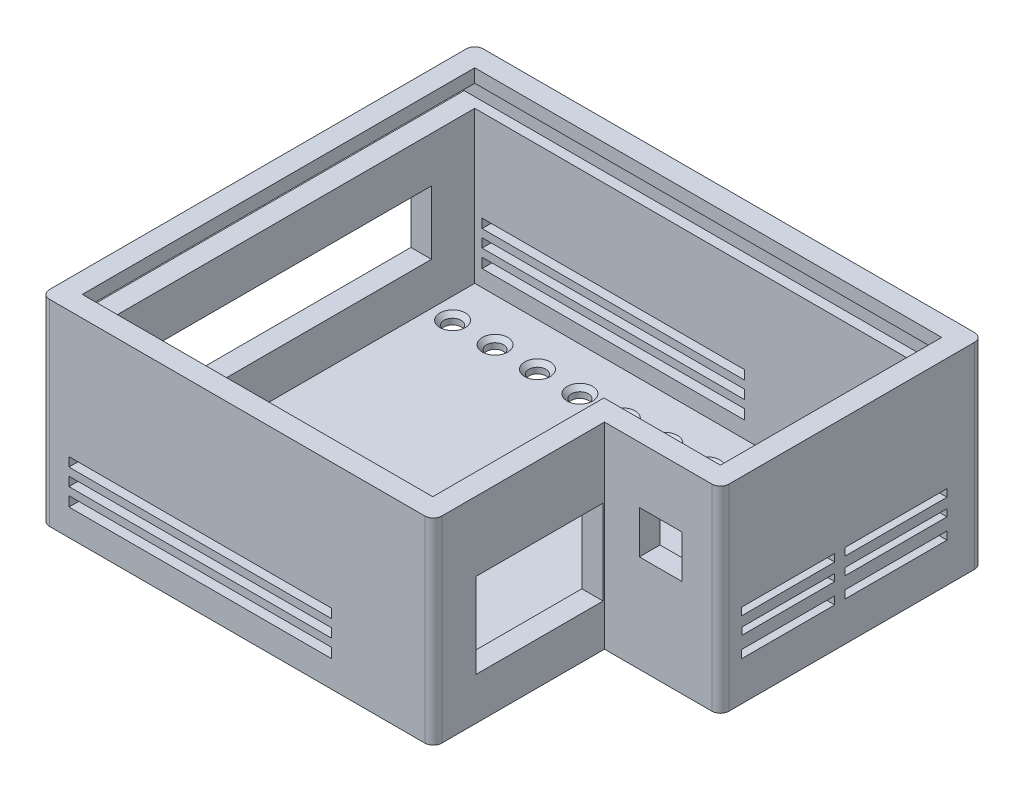
SolidWorks part; units mm, degrees
ref_plane "Front Plane" through (0, 0, 0) normal (0, 0, 1) x (1, 0, 0)
ref_plane "Top Plane" through (0, 0, 0) normal (0, 1, 0) x (1, 0, 0)
ref_plane "Right Plane" through (0, 0, 0) normal (1, 0, 0) x (0, 0, -1)
sketch "Sketch1" plane through (0, 0, 0) normal (0, 1, 0) x (1, 0, 0)
  line L0 (104.775, 0) -> (139.775, 0)
  line L1 (0, 0) -> (104.775, 0)
  line L2 (0, 0) -> (0, -117.475)
  line L3 (0, -117.475) -> (104.902, -117.475)
  line L4 (104.902, -66.2424) -> (104.902, -117.475)
  line L5 (139.775, 0) -> (139.775, -66.2424)
  line L6 (-3, -120.475) -> (104.902, -120.475)
  line L7 (104.902, -117.475) -> (104.902, -66.2424)
  line L8 (104.902, -66.2424) -> (139.775, -66.2424)
  line L9 (-3, 3) -> (-3, -120.475)
  line L10 (-3, 3) -> (104.775, 3)
  line L11 (104.775, 3) -> (142.775, 3)
  line L12 (142.775, 3) -> (142.775, -69.2424)
  line L13 (108.077, -69.2424) -> (142.775, -69.2424)
  line L14 (104.902, -66.2424) -> (107.9494, -66.2424)
  line L16 (108.077, -120.475) -> (104.902, -120.475)
  line L17 (-6.175, 6.175) -> (-6.175, -123.65)
  line L18 (104.902, -69.2424) -> (142.775, -69.2424) construction
  line L19 (-6.175, -123.65) -> (104.902, -123.65)
  line L20 (111.252, -123.65) -> (104.902, -123.65)
  line L21 (111.252, -72.4174) -> (111.252, -123.65)
  line L22 (111.252, -72.4174) -> (145.95, -72.4174)
  line L23 (145.95, 6.175) -> (145.95, -72.4174)
  line L24 (104.775, 6.175) -> (145.95, 6.175)
  line L25 (-6.175, 6.175) -> (104.775, 6.175)
  line L26 (108.077, -69.2424) -> (108.077, -120.475) construction
  dimension "D1" = 104.775
  dimension "D2" = 117.475
  dimension "D3" = 35
  dimension "D5" = 104.902
  dimension "D6" = 51.2326
  dimension "D8" = 51.2326
  dimension "D4" = 3
  dimension "D7" = 3.175
extrude "Boss-Extrude1" add sketch "Sketch1" along normal blind 55.88 contours L8 L4 L13 L12 L11 L10 L9 L6 L16 L7 L3 L2 L1 L0 L5 region at (49.3, 0, -4.1751)
ref_plane "Plane1" through (0, 0, 0) normal (0, 0, 1) x (1, 0, 0)
sketch "Sketch23" plane through (0, 0, 72.4174) normal (0, 0, 1) x (1, 0, 0)
  line L9 (121.6901, 38.9689) -> (134.3901, 38.9689)
  line L10 (121.6901, 38.9689) -> (121.6901, 26.1561)
  line L11 (121.6901, 26.1561) -> (134.3901, 26.1561)
  line L12 (134.3901, 38.9689) -> (134.3901, 26.1561)
  dimension "D1" = 12.8128
  dimension "D2" = 12.7
sketch "Sketch25" plane through (-6.175, 0, 0) normal (-1, 0, 0) x (0, 0, 1)
  line L1 (-6.175, 55.88) -> (-6.175, 0) construction
  line L4 (12.9455, 12.7) -> (101.8455, 12.7)
  line L5 (12.9455, 12.7) -> (12.9455, 31.75)
  line L6 (12.9455, 31.75) -> (101.8455, 31.75)
  line L7 (101.8455, 12.7) -> (101.8455, 31.75)
  dimension "D1" = 88.9
  dimension "D2" = 19.05
  dimension "D3" = 19.1205
extrude "Cut-Extrude9" cut sketch "Sketch25" against normal blind 45
sketch "Sketch26" plane through (145.95, 0, 0) normal (1, 0, 0) x (0, 0, -1)
  line L0 (-35.1213, 22.0738) -> (-4.5981, 22.0738)
  line L1 (-66.1038, 11.0882) -> (-38.1973, 11.0882)
  line L2 (-66.1038, 11.0882) -> (-66.1038, 8.7152)
  line L3 (-66.1038, 8.7152) -> (-38.1973, 8.7152)
  line L4 (-4.5981, 11.0882) -> (-4.5981, 8.7152)
  line L5 (-65.9512, 14.7529) -> (-38.1973, 14.7529)
  line L6 (-65.9512, 14.7529) -> (-65.9512, 16.8722)
  line L7 (-65.9512, 16.8722) -> (-38.1973, 16.8722)
  line L8 (-4.5981, 14.7529) -> (-4.5981, 16.8722)
  line L9 (-66.0841, 19.8363) -> (-38.1973, 19.8363)
  line L10 (-66.0841, 19.8363) -> (-66.0841, 22.0738)
  line L11 (-66.0841, 22.0738) -> (-38.1973, 22.0738)
  line L12 (-4.5981, 19.8363) -> (-4.5981, 22.0738)
  line L14 (-38.1973, 22.0738) -> (-38.1973, 19.8363)
  line L16 (-35.1213, 22.0738) -> (-35.1213, 19.8363)
  line L17 (-35.1213, 19.8363) -> (-4.5981, 19.8363)
  line L18 (-35.1213, 16.8722) -> (-35.1213, 14.7529)
  line L19 (-38.1973, 16.8722) -> (-38.1973, 14.7529)
  line L20 (-35.1213, 8.7152) -> (-4.5981, 8.7152)
  line L21 (-35.1213, 11.0882) -> (-4.5981, 11.0882)
  line L22 (-35.1213, 11.0882) -> (-35.1213, 8.7152)
  line L23 (-38.1973, 11.0882) -> (-38.1973, 8.7152)
  line L24 (-35.1213, 14.7529) -> (-4.5981, 14.7529)
  line L25 (-35.1213, 16.8722) -> (-4.5981, 16.8722)
extrude "Cut-Extrude10" cut sketch "Sketch26" against normal blind 45
sketch "Sketch27" plane through (0, 0, -6.175) normal (0, 0, -1) x (-1, 0, 0)
  line L1 (-2.1913, 4.9397) -> (-80.721, 4.9397)
  line L2 (-2.1913, 4.9397) -> (-2.1913, 7.8744)
  line L3 (-2.1913, 7.8744) -> (-80.721, 7.8744)
  line L4 (-80.721, 4.9397) -> (-80.721, 7.8744)
  line L5 (-80.721, 10.2406) -> (-2.1913, 10.2406)
  line L6 (-80.721, 10.2406) -> (-80.721, 12.9398)
  line L7 (-80.721, 12.9398) -> (-2.1913, 12.9398)
  line L8 (-2.1913, 10.2406) -> (-2.1913, 12.9398)
  line L9 (-2.1913, 15.306) -> (-80.721, 15.306)
  line L10 (-2.1913, 15.306) -> (-2.1913, 18.0154)
  line L11 (-2.1913, 18.0154) -> (-80.721, 18.0154)
  line L12 (-80.721, 15.306) -> (-80.721, 18.0154)
extrude "Cut-Extrude11" cut sketch "Sketch27" against normal blind 254
extrude "Cut-Extrude12" cut sketch "Sketch23" against normal blind 50.8
sketch "Sketch31" plane through (-6.175, 0, 0) normal (-1, 0, 0) x (0, 0, 1)
  line L3 (-3, 45.3704) -> (-3, 51.8754)
  line L4 (-3, 51.8754) -> (120.5647, 51.8754)
  line L7 (120.5647, 51.8754) -> (120.5647, 45.3704)
  line L8 (120.5647, 45.3704) -> (-3, 45.3704)
extrude "Cut-Extrude13" cut sketch "Sketch31" against normal blind 113.8
sketch "Sketch34" plane through (107.625, 0, 0) normal (-1, 0, 0) x (0, 0, 1)
  line L1 (66.2424, 45.3704) -> (69.0364, 45.3704)
  line L2 (66.2424, 45.3704) -> (66.2424, 51.3704)
  line L3 (66.2424, 51.3704) -> (69.0364, 51.3704)
  line L4 (69.0364, 45.3704) -> (69.0364, 51.3704)
  line L5 (-3, 45.3704) -> (0, 45.3704)
  line L6 (-3, 45.3704) -> (-3, 51.8754)
  line L7 (-3, 51.8754) -> (0, 51.8754)
  line L8 (0, 45.3704) -> (0, 51.8754)
  dimension "D1" = 6
  dimension "D2" = 2.794
extrude "Cut-Extrude14" cut sketch "Sketch34" against normal blind 35.8
sketch "Sketch35" plane through (139.775, 0, 0) normal (-1, 0, 0) x (0, 0, 1)
  line L1 (0, 45.3704) -> (66.2424, 45.3704)
  line L2 (0, 45.3704) -> (0, 51.3704)
  line L3 (0, 51.3704) -> (66.2424, 51.3704)
  line L4 (66.2424, 45.3704) -> (66.2424, 51.3704)
extrude "Cut-Extrude15" cut sketch "Sketch35" against normal blind 2.8
sketch "Sketch36" plane through (0, 0, 0) normal (0, -1, 0) x (1, 0, 0)
  line L0 (111.252, 72.4174) -> (111.252, 123.65)
  line L1 (111.252, 123.65) -> (-6.175, 123.65)
  line L2 (-6.175, 123.65) -> (-6.175, -6.175)
  line L3 (-6.175, -6.175) -> (145.95, -6.175)
  line L4 (145.95, -6.175) -> (145.95, 72.4174)
  line L5 (145.95, 72.4174) -> (111.252, 72.4174)
extrude "Boss-Extrude2" add sketch "Sketch36" along normal blind 3
ref_plane "Plane2" through (145.95, -3, 72.4174) normal (0, -1, 0) x (-1, 0, 0)
sketch "Sketch37" plane through (145.95, -3, 72.4174) normal (0, -1, 0) x (1, 0, 0)
  line L0 (0, -78.5924) -> (0, 0) construction
  line L1 (-152.125, -78.5924) -> (0, -78.5924) construction
  circle A22 centre (-12.7, -59.5424) radius 2.54
  circle A26 centre (-63.5, 29.3576) radius 2.54
  circle A27 centre (-114.3, 29.3576) radius 2.54
  circle A28 centre (-25.4, -59.5424) radius 2.54
  circle A29 centre (-38.1, -59.5424) radius 2.54
  circle A30 centre (-50.8, -59.5424) radius 2.54
  circle A31 centre (-63.5, -59.5424) radius 2.54
  circle A32 centre (-76.2, -59.5424) radius 2.54
  circle A33 centre (-88.9, -59.5424) radius 2.54
  circle A34 centre (-101.6, -59.5424) radius 2.54
  circle A35 centre (-114.3, -59.5424) radius 2.54
  circle A36 centre (-127, -59.5424) radius 2.54
  circle A37 centre (-139.7, -59.5424) radius 2.54
  dimension "D1" = 5.08
  dimension "D2" = 12.7
  dimension "D3" = 19.05
  dimension "D5" = 88.9
  dimension "D7" = 5.08
  dimension "D8" = 5.08
  dimension "D9" = 11
  dimension "D12" = 88.9
  dimension "D15" = 50.8
sketch "Sketch38" plane through (111.252, 0, 0) normal (1, 0, 0) x (0, 0, -1)
  line L0 (-72.4174, -3) -> (-123.65, -3) construction
  line L1 (-110.95, 35.1) -> (-72.85, 35.1)
  line L2 (-110.95, 35.1) -> (-110.95, 9.7)
  line L3 (-110.95, 9.7) -> (-72.85, 9.7)
  line L4 (-72.85, 35.1) -> (-72.85, 9.7)
  line L5 (-123.65, 55.88) -> (-123.65, -3) construction
  dimension "D1" = 12.7
  dimension "D2" = 12.7
  dimension "D3" = 50.8
  dimension "D4" = 38.1
extrude "Cut-Extrude17" cut sketch "Sketch38" against normal blind 10.16
fillet "Fillet1" radius 2.54 5 edges at (-6.175, 26.44, 123.65) (-6.175, 26.44, -6.175) (111.252, 26.44, 123.65) (145.95, 26.44, 72.4174) (145.95, 26.44, -6.175)
extrude "Cut-Extrude18" cut sketch "Sketch37" against normal blind 5.842
chamfer "Chamfer1" distance 1.27 angle 45 13 edges at (31.65, 0, 104.315) (82.45, 0, 104.315) (6.25, 0, 15.415) (18.95, 0, 15.415) (31.65, 0, 15.415) (44.35, 0, 15.415) (57.05, 0, 15.415) (69.75, 0, 15.415) (82.45, 0, 15.415) (95.15, 0, 15.415) (107.85, 0, 15.415) (120.55, 0, 15.415) (133.25, 0, 15.415)
